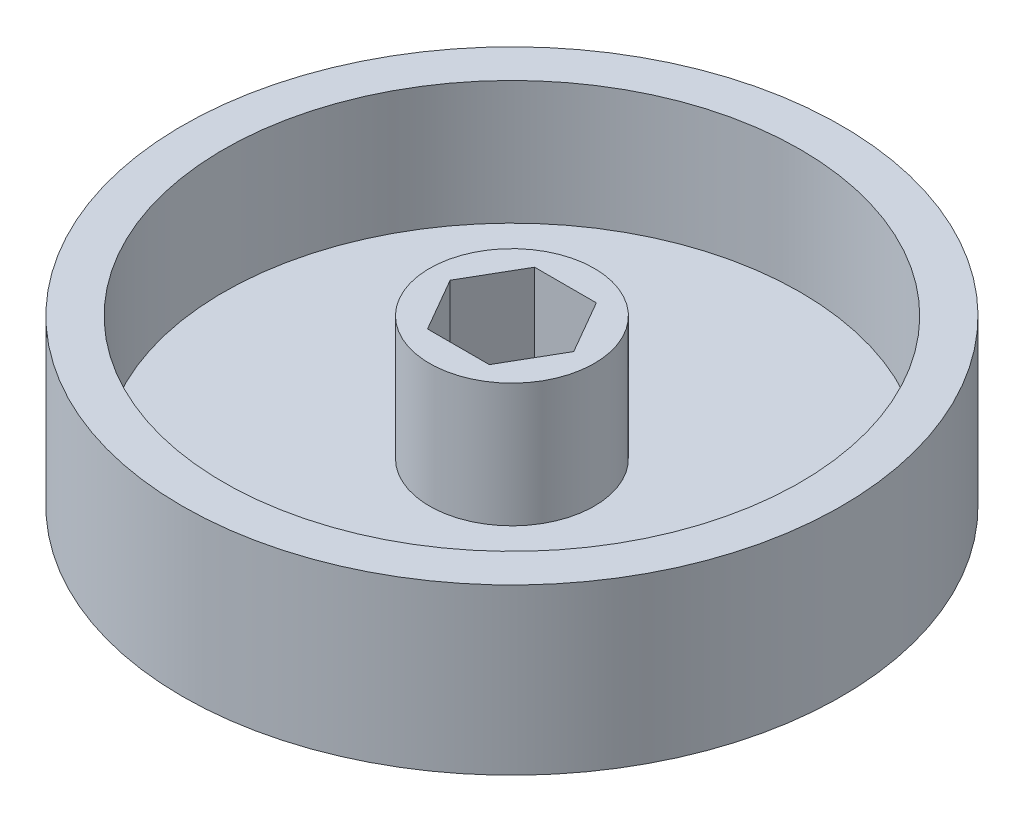
SolidWorks part; units mm, degrees
ref_plane "Front Plane" through (0, 0, 0) normal (0, 0, 1) x (1, 0, 0)
ref_plane "Top Plane" through (0, 0, 0) normal (0, 1, 0) x (1, 0, 0)
ref_plane "Right Plane" through (0, 0, 0) normal (1, 0, 0) x (0, 0, -1)
sketch "Sketch1" plane through (0, 0, 0) normal (0, 1, 0) x (1, 0, 0)
  circle A0 centre (0, 0) radius 50.8
  dimension "D1" = 101.6
extrude "Boss-Extrude1" add sketch "Sketch1" along normal blind 6.35
sketch "Sketch4" plane through (0, 6.35, 0) normal (0, 1, 0) x (1, 0, 0)
  circle A0 centre (0, 0) radius 50.8
  circle A1 centre (0, 0) radius 44.45
  dimension "D1" = 6.35
extrude "Boss-Extrude2" add sketch "Sketch4" along normal blind 19.05
sketch "Sketch5" plane through (0, 6.35, 0) normal (0, 1, 0) x (1, 0, 0)
  line L0 (0, 0) -> (8.5165, -9.4212)
  circle A0 centre (0, 0) radius 12.7
  dimension "D1" = 12.7
extrude "Boss-Extrude3" add sketch "Sketch5" along normal blind 19.05 contours A0 region at (11.2788, 6.35, 5.0084)
sketch "Sketch6" plane through (0, 25.4, 0) normal (0, 1, 0) x (1, 0, 0)
  line L0 (9.525, 0) -> (12.7, 0)
  line L1 (9.525, 0) -> (4.7625, 8.2489)
  line L2 (4.7625, 8.2489) -> (-4.7625, 8.2489)
  line L3 (-4.7625, 8.2489) -> (-9.525, 0)
  line L4 (-9.525, 0) -> (-4.7625, -8.2489)
  line L5 (-4.7625, -8.2489) -> (4.7625, -8.2489)
  line L6 (4.7625, -8.2489) -> (9.525, 0)
  circle A1 centre (0, 0) radius 8.2489 construction
  circle A2 centre (0, 0) radius 12.7 construction
  dimension "D1" = 3.175
extrude "Cut-Extrude1" cut sketch "Sketch6" against normal blind 25.4 contours L5 L6 L1 L2 L3 L4 region at (0, 25.4, 0)
ref_axis "Axis1" through (0, 25.4, 0) along (0, -1, 0)
